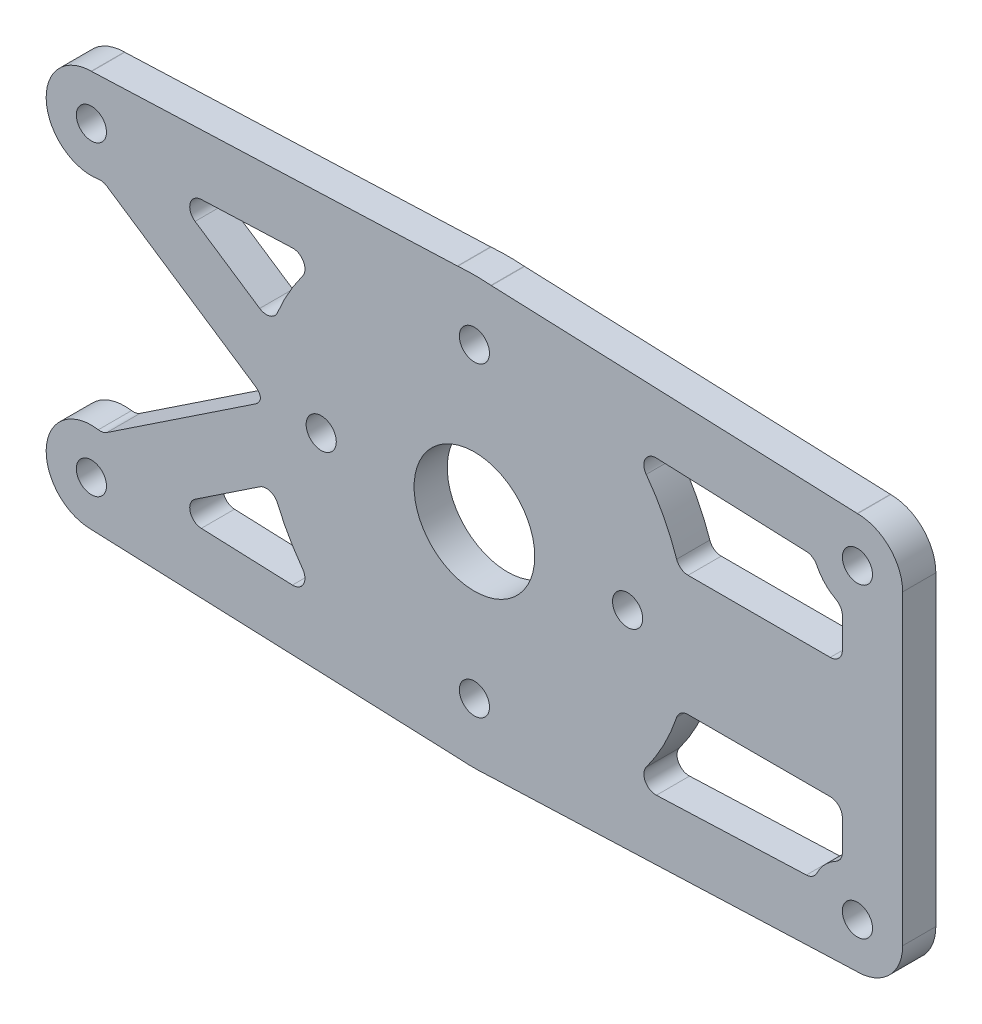
SolidWorks part; units mm, degrees
ref_plane "Front Plane" through (0, 0, 0) normal (0, 0, 1) x (1, 0, 0)
ref_plane "Top Plane" through (0, 0, 0) normal (0, 1, 0) x (1, 0, 0)
ref_plane "Right Plane" through (0, 0, 0) normal (1, 0, 0) x (0, 0, -1)
sketch "Sketch1" plane through (0, 0, 0) normal (0, 0, 1) x (1, 0, 0)
  line L0 (55, 0) -> (-55, 0) construction
  circle A0 centre (0, 0) radius 10
  circle A1 centre (0, 0) radius 25.4 construction
  circle A2 centre (0, 25.4) radius 2.5
  circle A3 centre (25.4, 0) radius 2.5
  circle A4 centre (0, -25.4) radius 2.5
  circle A5 centre (-25.4, 0) radius 2.5
  circle A6 centre (0, 0) radius 35.4
  circle A7 centre (-63.5, 25.4) radius 2.5
  circle A8 centre (63.5, 25.4) radius 2.5
  circle A9 centre (63.5, -25.4) radius 2.5
  circle A10 centre (-63.5, -25.4) radius 2.5
  circle A11 centre (-63.5, 25.4) radius 7.5
  circle A12 centre (-63.5, -25.4) radius 7.5
  circle A13 centre (63.5, 25.4) radius 7.5
  circle A14 centre (63.5, -25.4) radius 7.5
  point P8 (0, 0)
  point P15 (0, 0)
  point P20 (0, 0)
  dimension "D1" = 20
  dimension "D2" = 50.8
  dimension "D3" = 5
  dimension "D9" = 5
  dimension "D6" = 127
  dimension "D7" = 63.5
  dimension "D8" = 25.4
  dimension "D5" = 10
  dimension "D10" = 5
  dimension "D4" = 4
extrude "Boss-Extrude1" add sketch "Sketch1" along normal mid plane 5.5
sketch "Sketch2" plane through (0, 0, 2.75) normal (0, 0, 1) x (1, 0, 0)
  line L0 (-71, 25.4) -> (-71, -25.4)
  line L1 (71, 25.4) -> (71, -25.4)
  line L2 (-63.5, 32.9) -> (0, 35.4)
  line L3 (0, 35.4) -> (63.5, 32.9)
  line L4 (-63.5, -32.9) -> (0, -35.4)
  line L5 (63.5, -32.9) -> (0, -35.4)
  line L6 (-63.1066, -22.9077) -> (0, -25.3923)
  line L7 (63.1066, -22.9077) -> (0, -25.3923)
  line L8 (-61, 25.4) -> (-61, -25.4)
  line L9 (-63.1066, 22.9077) -> (0, 25.3923)
  line L10 (0, 25.3923) -> (63.1066, 22.9077)
  line L11 (61, 25.4) -> (61, -25.4)
  line L12 (-71, 0) -> (71, 0) construction
  line L13 (-71, -10) -> (71, -10)
  line L14 (-71, 10) -> (71, 10)
  circle A0 centre (-63.5, -25.4) radius 7.5 construction
  circle A1 centre (-63.5, 25.4) radius 7.5 construction
  circle A2 centre (-63.5, -25.4) radius 7.5
  circle A3 centre (-63.5, 25.4) radius 7.5
  circle A4 centre (0, 0) radius 35.4 construction
  circle A5 centre (63.5, -25.4) radius 7.5 construction
  circle A6 centre (63.5, 25.4) radius 7.5 construction
  circle A7 centre (0, 0) radius 35.4
  circle A8 centre (63.5, -25.4) radius 7.5
  circle A9 centre (63.5, 25.4) radius 7.5
  circle M12 centre (-63.5, 25.4) radius 7.5
  dimension "D1" = 10
  dimension "D2" = 10
  dimension "D3" = 10
  dimension "D4" = 10
extrude "Boss-Extrude2" add sketch "Sketch2" against normal up to surface (5.5 mm away) contours A8 L1 L13 L11 | L12 L11 L13 L1 | L11 L12 L1 L14 | A9 L11 L14 L1 | A9 L3 A7 L10 | A7 L12 L11 L14 | L12 A7 L13 L11 | A7 L2 L9 M12 | A7 L6 A2 L4 | A8 L7 A7 L5 region at (-37.418, 29.429, 2.75) region at (47.9582, 5.0459, 2.75) region at (37.418, 29.429, 2.75) region at (-37.418, -29.429, 2.75) region at (47.9582, -5.0459, 2.75) region at (66, 5, 2.75) region at (66.4221, 14.7085, 2.75) region at (66, -5, 2.75) region at (66.4221, -14.7085, 2.75) region at (37.418, -29.429, 2.75) up to face at (-56, 25.4, -2.75)
sketch "Sketch4" plane through (0, 0, 2.75) normal (0, 0, 1) x (1, 0, 0)
  line L0 (-63.5, 25.4) -> (-25.4, 0) construction
  line L1 (-25.4, 0) -> (-63.5, -25.4) construction
  line L2 (-66.2735, 21.2397) -> (-34.4139, 0)
  line L3 (-34.4139, 0) -> (-66.2735, -21.2397)
  line L4 (-60.7265, 29.5603) -> (-16.3861, 0)
  line L5 (-16.3861, 0) -> (-60.7265, -29.5603)
  line L13 (-2.7831, 35.2904) -> (-63.5, 32.9)
  line L14 (-56.3379, 23.1742) -> (-25.6649, 24.3818)
  line L15 (-25.6649, -24.3818) -> (-56.3379, -23.1742)
  line L16 (-63.5, -32.9) -> (-2.7831, -35.2904)
  line L17 (2.7831, -35.2904) -> (63.5, -32.9)
  line L18 (71, -25.4) -> (71, 25.4)
  line L19 (63.5, 32.9) -> (2.7831, 35.2904)
  line L20 (-2.7831, 35.2904) -> (-63.5, 32.9)
  line L21 (-56.3379, 23.1742) -> (-25.6649, 24.3818)
  line L22 (-25.6649, -24.3818) -> (-56.3379, -23.1742)
  line L23 (-63.5, -32.9) -> (-2.7831, -35.2904)
  line L24 (2.7831, -35.2904) -> (63.5, -32.9)
  line L25 (71, -25.4) -> (71, 25.4)
  line L26 (63.5, 32.9) -> (2.7831, 35.2904)
  arc A7 (2.7831, 35.2904) -> (-2.7831, 35.2904) centre (0, 0) ccw
  arc A8 (-63.5, 32.9) -> (-56.3379, 23.1742) centre (-63.5, 25.4) ccw
  arc A9 (-25.6649, 24.3818) -> (-25.6649, -24.3818) centre (0, 0) ccw
  arc A10 (-56.3379, -23.1742) -> (-63.5, -32.9) centre (-63.5, -25.4) ccw
  arc A11 (-2.7831, -35.2904) -> (2.7831, -35.2904) centre (0, 0) ccw
  arc A12 (63.5, -32.9) -> (71, -25.4) centre (63.5, -25.4) ccw
  arc A13 (71, 25.4) -> (63.5, 32.9) centre (63.5, 25.4) ccw
  arc A14 (2.7831, 35.2904) -> (-2.7831, 35.2904) centre (0, 0) ccw
  arc A15 (-63.5, 32.9) -> (-56.3379, 23.1742) centre (-63.5, 25.4) ccw
  arc A16 (-25.6649, 24.3818) -> (-25.6649, -24.3818) centre (0, 0) ccw
  arc A17 (-56.3379, -23.1742) -> (-63.5, -32.9) centre (-63.5, -25.4) ccw
  arc A18 (-2.7831, -35.2904) -> (2.7831, -35.2904) centre (0, 0) ccw
  arc A19 (63.5, -32.9) -> (71, -25.4) centre (63.5, -25.4) ccw
  arc A20 (71, 25.4) -> (63.5, 32.9) centre (63.5, 25.4) ccw
  arc M31 (-63.5, 32.9) -> (-56.3379, 23.1742) centre (-63.5, 25.4) ccw
  line M32 (-56.3379, 23.1742) -> (-25.6649, 24.3818)
  arc M33 (-25.6649, 24.3818) -> (-25.6649, -24.3818) centre (0, 0) ccw
  line M34 (-25.6649, -24.3818) -> (-56.3379, -23.1742)
  arc M35 (-56.3379, -23.1742) -> (-63.5, -32.9) centre (-63.5, -25.4) ccw
  dimension "D1" = 5
  dimension "D2" = 5
  dimension "D3" = 0
extrude "Boss-Extrude3" add sketch "Sketch4" against normal up to surface (5.5 mm away) contours L4 L2 M32 M31 M33 | L5 L3 M33 M35 M34 region at (-46.054, 13.4685, 2.75) region at (-46.054, -13.4685, 2.75) up to face at (-3.4196, 0, -2.75)
fillet "Fillet2" radius 2 28 edges at (25.6649, 24.3818, 0) (56.3379, 23.1742, 0) (61, 18.3289, 0) (61, 10, 0) (33.9582, 10, 0) (61, -10, 0) (61, -18.3289, 0) (56.3379, -23.1742, 0) (25.6649, -24.3818, 0) (33.9582, -10, 0) (-51.4369, 23.3672, 0) (-33.509, 11.4152, 0) (-33.509, -11.4152, 0) (-25.6649, -24.3818, 0) (-51.4369, -23.3672, 0) (-25.6649, 24.3818, 0) (-61.6222, -18.1389, 0) (-63.5, -32.9, 0) (-2.7831, -35.2904, 0) (2.7831, -35.2904, 0) (63.5, -32.9, 0) (63.5, 32.9, 0) (2.7831, 35.2904, 0) (-2.7831, 35.2904, 0) (-63.5, 32.9, 0) (-35.394, 0.6534, 0) (-35.394, -0.6534, 0) (-61.6222, 18.1389, 0)
